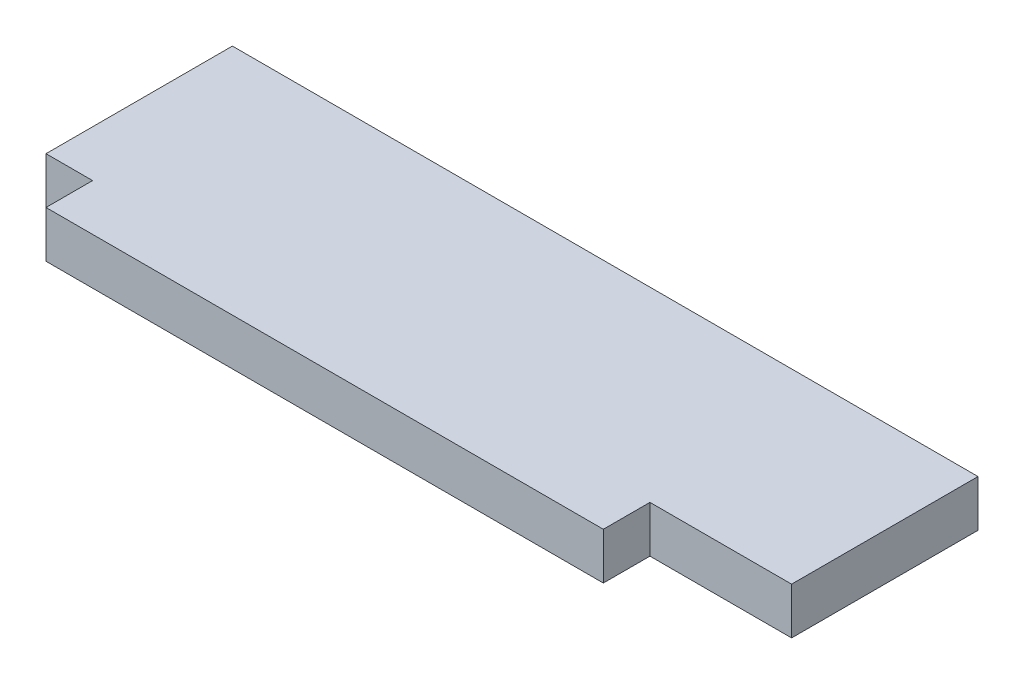
SolidWorks part; units mm, degrees
ref_plane "Front Plane" through (0, 0, 0) normal (0, 0, 1) x (1, 0, 0)
ref_plane "Top Plane" through (0, 0, 0) normal (0, 1, 0) x (1, 0, 0)
ref_plane "Right Plane" through (0, 0, 0) normal (1, 0, 0) x (0, 0, -1)
sketch "Sketch1" plane through (0, 0, 0) normal (0, 1, 0) x (1, 0, 0)
  line L1 (0, 0) -> (80, 0)
  line L2 (0, 0) -> (0, 20)
  line L3 (0, 20) -> (80, 20)
  line L4 (80, 0) -> (80, 20)
  line L5 (5, 0) -> (64.8, 0)
  line L6 (5, 0) -> (5, -5)
  line L7 (5, -5) -> (64.8, -5)
  line L8 (64.8, 0) -> (64.8, -5)
  dimension "D1" = 80
  dimension "D2" = 20
  dimension "D3" = 59.8
  dimension "D4" = 5
  dimension "D5" = 5
extrude "Boss-Extrude1" add sketch "Sketch1" along normal blind 5 contours L1 L4 L3 L2 | L8 L1 L6 L7 region at (40, 0, -10) region at (34.9, 0, 2.5)
